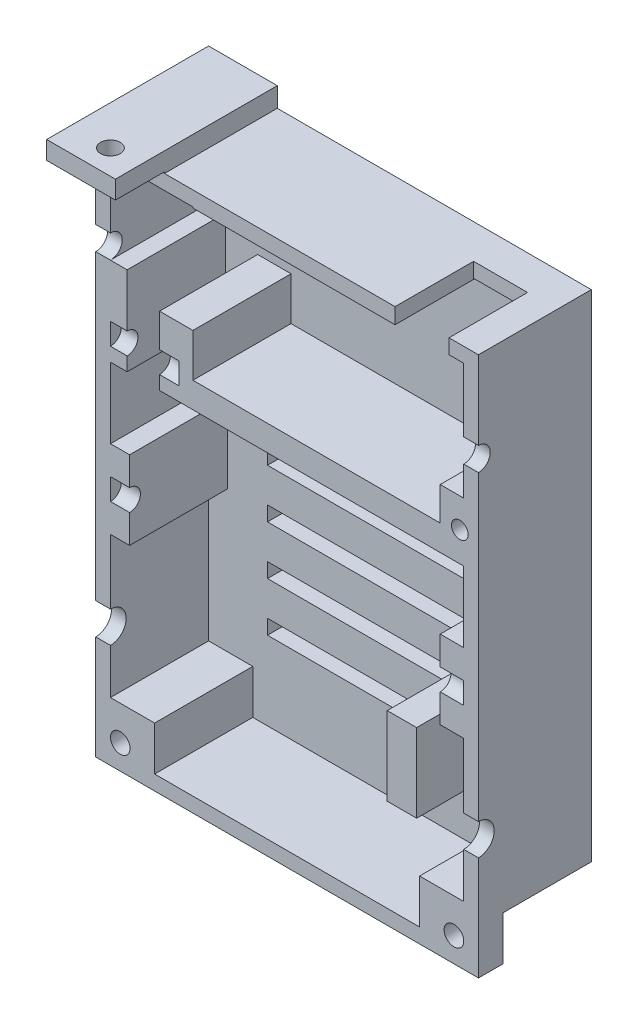
SolidWorks part; units mm, degrees
ref_plane "前视基准面" through (0, 0, 0) normal (0, 0, 1) x (1, 0, 0)
ref_plane "上视基准面" through (0, 0, 0) normal (0, 1, 0) x (1, 0, 0)
ref_plane "右视基准面" through (0, 0, 0) normal (1, 0, 0) x (0, 0, -1)
other "Configuration Table"
sketch "草图1" plane through (0, 0, 0) normal (0, 0, 1) x (1, 0, 0)
  line L1 (19.5, 27.5) -> (-19.5, 27.5)
  line L2 (19.5, 27.5) -> (19.5, -27.5)
  line L3 (19.5, -27.5) -> (-19.5, -27.5)
  line L4 (-19.5, 27.5) -> (-19.5, -27.5)
  line L5 (19.5, 27.5) -> (-19.5, -27.5) construction
  line L6 (19.5, -27.5) -> (-19.5, 27.5) construction
  point P0 (0, 0)
  dimension "D1" = 55
  dimension "D2" = 39
extrude "凸台-拉伸1" add sketch "草图1" along normal blind 11.5
shell "抽壳1" thickness 1.5 removed face at (0, 0, 11.5)
sketch "草图2" plane through (0, 0, 0) normal (0, 0, -1) x (-1, 0, 0)
  line L0 (-19.5, 27.5) -> (19.5, 27.5) construction
  line L1 (19.5, 29.5) -> (12.5, 29.5)
  line L2 (19.5, 29.5) -> (19.5, 27.5)
  line L3 (19.5, 27.5) -> (12.5, 27.5)
  line L4 (12.5, 29.5) -> (12.5, 27.5)
  line L6 (19.5, 27.5) -> (19.5, -27.5) construction
  dimension "D2" = 2
  dimension "D3" = 7
extrude "凸台-拉伸2" add sketch "草图2" against normal offset from surface (16.5 mm away) 5 separate body up to face at (0, 0, 11.5) offset beyond the face yes
sketch "草图3" plane through (0, 29.5, 0) normal (0, 1, 0) x (1, 0, 0)
  circle A0 centre (-15.502, -14) radius 1
  dimension "D1" = 2
extrude "切除-拉伸1" cut sketch "草图3" against normal up to next (2 mm away)
sketch "草图4" plane through (0, 27.5, 0) normal (0, 1, 0) x (1, 0, 0)
  line L0 (19.5, -11.5) -> (-19.5, -11.5) construction
  line L1 (11, -3.5) -> (16.5, -3.5)
  line L2 (11, -3.5) -> (11, -11.5)
  line L3 (11, -11.5) -> (16.5, -11.5)
  line L4 (16.5, -3.5) -> (16.5, -11.5)
  line L5 (16.5, -7.5) -> (16.5, -3.5) construction
extrude "切除-拉伸2" cut sketch "草图4" against normal up to next (1.5 mm away)
sketch "草图5" plane through (-19.5, 0, 0) normal (-1, 0, 0) x (0, 0, 1)
  circle A0 centre (11.5, 18.3) radius 1.2
  arc A1 (11.5, 17.1) -> (11.5, 19.5) centre (11.5, 18.3) ccw construction
  circle A3 centre (11.5, -15.3) radius 1.6
  arc A4 (11.5, -16.9) -> (11.5, -13.7) centre (11.5, -15.3) ccw construction
extrude "切除-拉伸3" cut sketch "草图5" against normal through all
sketch "草图8" plane through (0, 0, 0) normal (0, 0, -1) x (-1, 0, 0)
  line L0 (18, 0.9) -> (16.05, 0.9) construction
  line L1 (16.05, -7.1) -> (18, -7.1) construction
  line L6 (-18, -7.1) -> (-15.6, -7.1) construction
  line L7 (-15.6, 0.9) -> (-18, 0.9) construction
  line L8 (-15.6, 14.1) -> (-18, 14.1) construction
  line L9 (-15.6, 10.7) -> (-15.6, 14.1) construction
  line L10 (9.6, 10.7) -> (-15.6, 10.7) construction
  line L11 (9.6, 15.1) -> (9.6, 10.7) construction
  line L12 (-18, 8.1) -> (13, 8.1) construction
  line L13 (13, 15.1) -> (9.6, 15.1) construction
  line L14 (16.3, 8.1) -> (18, 8.1) construction
  line L15 (18, 17.1) -> (16.3, 17.1) construction
  line L16 (18, 0.9) -> (16.05, 0.9)
  line L17 (16.05, -7.1) -> (18, -7.1)
  line L22 (-18, -7.1) -> (-15.6, -7.1)
  line L23 (-15.6, 0.9) -> (-18, 0.9)
  line L24 (-15.6, 14.1) -> (-18, 14.1)
  line L25 (-15.6, 10.7) -> (-15.6, 14.1)
  line L26 (9.6, 10.7) -> (-15.6, 10.7)
  line L27 (9.6, 15.1) -> (9.6, 10.7)
  line L28 (-18, 8.1) -> (13, 8.1)
  line L29 (13, 15.1) -> (9.6, 15.1)
  line L30 (16.3, 8.1) -> (18, 8.1)
  line L31 (18, 17.1) -> (16.3, 17.1)
  line L32 (18, 8.1) -> (18, 17.1)
  line L33 (16.3, 17.1) -> (16.3, 8.1)
  line L34 (13, 8.1) -> (13, 15.1)
  line L35 (-18, 14.1) -> (-18, 8.1)
  line L36 (-15.6, -7.1) -> (-15.6, 0.9)
  line L37 (-18, 0.9) -> (-18, -7.1)
  line L38 (18, -7.1) -> (18, 0.9)
  line L39 (16.05, 0.9) -> (16.05, -7.1)
  line L40 (18, -21.5) -> (13.5, -21.5) construction
  line L41 (13.5, -21.5) -> (13.5, -26) construction
  line L42 (-13.5, -26) -> (-13.5, -21.5) construction
  line L43 (-13.5, -21.5) -> (-18, -21.5) construction
  line L44 (18, -21.5) -> (13.5, -21.5)
  line L45 (13.5, -21.5) -> (13.5, -26)
  line L46 (-13.5, -26) -> (-13.5, -21.5)
  line L47 (-13.5, -21.5) -> (-18, -21.5)
  line L48 (18, -21.5) -> (18, -26)
  line L49 (18, -26) -> (13.5, -26)
  line L50 (-13.5, -26) -> (-18, -26)
  line L51 (-18, -26) -> (-18, -21.5)
  line L52 (-11, 25.9) -> (9.6, 25.9) construction
  line L53 (-11, 25.9) -> (9.6, 25.9)
  line L55 (9.6, 25.9) -> (9.6, 26)
  line L56 (9.6, 26) -> (-11, 26)
  line L57 (-11, 26) -> (-11, 25.9)
extrude "凸台-拉伸3" add sketch "草图8" against normal blind 11.5
sketch "草图7" plane through (-19.5, 0, 0) normal (-1, 0, 0) x (0, 0, 1)
  circle A0 centre (11.5, -3.1) radius 1.1
  dimension "D1" = 2.2
sketch "草图10" plane through (-19.5, 0, 0) normal (-1, 0, 0) x (0, 0, 1)
  circle A0 centre (11.5, 10.6) radius 1.1
  dimension "D1" = 2.2
extrude "切除-拉伸12" cut sketch "草图10" against normal blind 7 from offset 1.5 offset against normal yes
extrude "切除-拉伸13" cut sketch "草图7" against normal offset from surface (36 mm away) 1.5 from offset 1.5 up to face at (19.5, 0.75, 8.275) offset against normal yes
sketch "草图13" plane through (0, 0, 0) normal (0, 0, -1) x (-1, 0, 0)
  line L0 (13.5, -26) -> (-13.5, -26) construction
  line L1 (12, -16.5) -> (-12, -16.5)
  line L2 (12, -16.5) -> (12, -18)
  line L3 (12, -18) -> (-12, -18)
  line L4 (-12, -16.5) -> (-12, -18)
  line L5 (0, 0) -> (0, 20.7312) construction
  line L6 (12, -11.5) -> (-12, -11.5)
  line L7 (12, -11.5) -> (12, -13)
  line L8 (12, -13) -> (-12, -13)
  line L9 (-12, -11.5) -> (-12, -13)
  line L10 (12, -6.5) -> (-12, -6.5)
  line L11 (12, -6.5) -> (12, -8)
  line L12 (12, -8) -> (-12, -8)
  line L13 (-12, -6.5) -> (-12, -8)
  line L14 (12, -1.5) -> (-12, -1.5)
  line L15 (12, -1.5) -> (12, -3)
  line L16 (12, -3) -> (-12, -3)
  line L17 (-12, -1.5) -> (-12, -3)
  line L18 (12, 3.5) -> (-12, 3.5)
  line L19 (12, 3.5) -> (12, 2)
  line L20 (12, 2) -> (-12, 2)
  line L21 (-12, 3.5) -> (-12, 2)
  line L22 (12, 8.5) -> (-12, 8.5)
  line L23 (12, 8.5) -> (12, 7)
  line L24 (12, 7) -> (-12, 7)
  line L25 (-12, 8.5) -> (-12, 7)
  dimension "D1" = 1.5
  dimension "D2" = 8
  dimension "D3" = 24
  dimension "D4" = 6
extrude "切除-拉伸14" cut sketch "草图13" against normal blind 1.5
sketch "草图12" plane through (0, 0, 0) normal (0, 0, -1) x (-1, 0, 0)
  line L0 (-10.2, -19.55) -> (-7.2, -19.55) construction
  line L1 (-10.2, -11.55) -> (-10.2, -19.55) construction
  line L2 (-7.2, -11.55) -> (-10.2, -11.55) construction
  line L3 (-7.2, -19.55) -> (-7.2, -11.55) construction
  line L4 (-10.2, -19.55) -> (-7.2, -19.55)
  line L5 (-10.2, -11.55) -> (-10.2, -19.55)
  line L6 (-7.2, -11.55) -> (-10.2, -11.55)
  line L7 (-7.2, -19.55) -> (-7.2, -11.55)
extrude "凸台-拉伸4" add sketch "草图12" against normal blind 8.5
sketch "草图14" plane through (0, 0, 16.5) normal (0, 0, 1) x (1, 0, 0)
  line L0 (-19.5, 29.5) -> (-19.5, 27.5) construction
  line L1 (-19.5, 27.65) -> (-12.5, 27.65)
  line L2 (-19.5, 27.65) -> (-19.5, 27.5)
  line L3 (-19.5, 27.5) -> (-12.5, 27.5)
  line L4 (-12.5, 27.65) -> (-12.5, 27.5)
  dimension "D1" = 0.15
extrude "切除-拉伸15" cut sketch "草图14" against normal up to surface (5 mm away) up to face at (-9.025, 24.725, 11.5)
sketch "草图15" plane through (0, 0, 0) normal (0, 0, -1) x (-1, 0, 0)
  line L0 (19.5, -27.5) -> (-19.5, -27.5) construction
  line L1 (15, -23) -> (19.5, -23)
  line L2 (15, -23) -> (15, -27.5)
  line L3 (15, -27.5) -> (19.5, -27.5)
  line L4 (19.5, -23) -> (19.5, -27.5)
  line L5 (-15, -23) -> (-19.5, -23)
  line L6 (-15, -23) -> (-15, -27.5)
  line L7 (-15, -27.5) -> (-19.5, -27.5)
  line L8 (-19.5, -23) -> (-19.5, -27.5)
  line L9 (-19.5, -27.5) -> (-19.5, 27.5) construction
  line L10 (-13.5, -26) -> (-13.5, -21.5) construction
  line L11 (-13.5, -21.5) -> (-18, -21.5) construction
  line L12 (13.5, -21.5) -> (13.5, -26) construction
  line L13 (18, -21.5) -> (13.5, -21.5) construction
  dimension "D1" = 1.5
  dimension "D2" = 1.5
  dimension "D3" = 1.5
  dimension "D4" = 1.5
extrude "切除-拉伸16" cut sketch "草图15" against normal offset from surface (9 mm away) 2.5 up to face at (-9.025, 24.725, 11.5)
sketch "草图16" plane through (0, 0, 9) normal (0, 0, -1) x (-1, 0, 0)
  circle A0 centre (-17, -25) radius 1
  circle A1 centre (17, -25) radius 1
  dimension "D1" = 2
  dimension "D2" = 2
extrude "切除-拉伸17" cut sketch "草图16" against normal up to next (2.5 mm away)
sketch "草图17" plane through (0, 0, 0) normal (0, 0, -1) x (-1, 0, 0)
  circle A0 centre (-17.6, 11.1) radius 0.85
  dimension "D1" = 1.7
extrude "切除-拉伸18" cut sketch "草图17" along normal blind 2.5 from surface starting at face at (18, 24.3333, 11.5)
